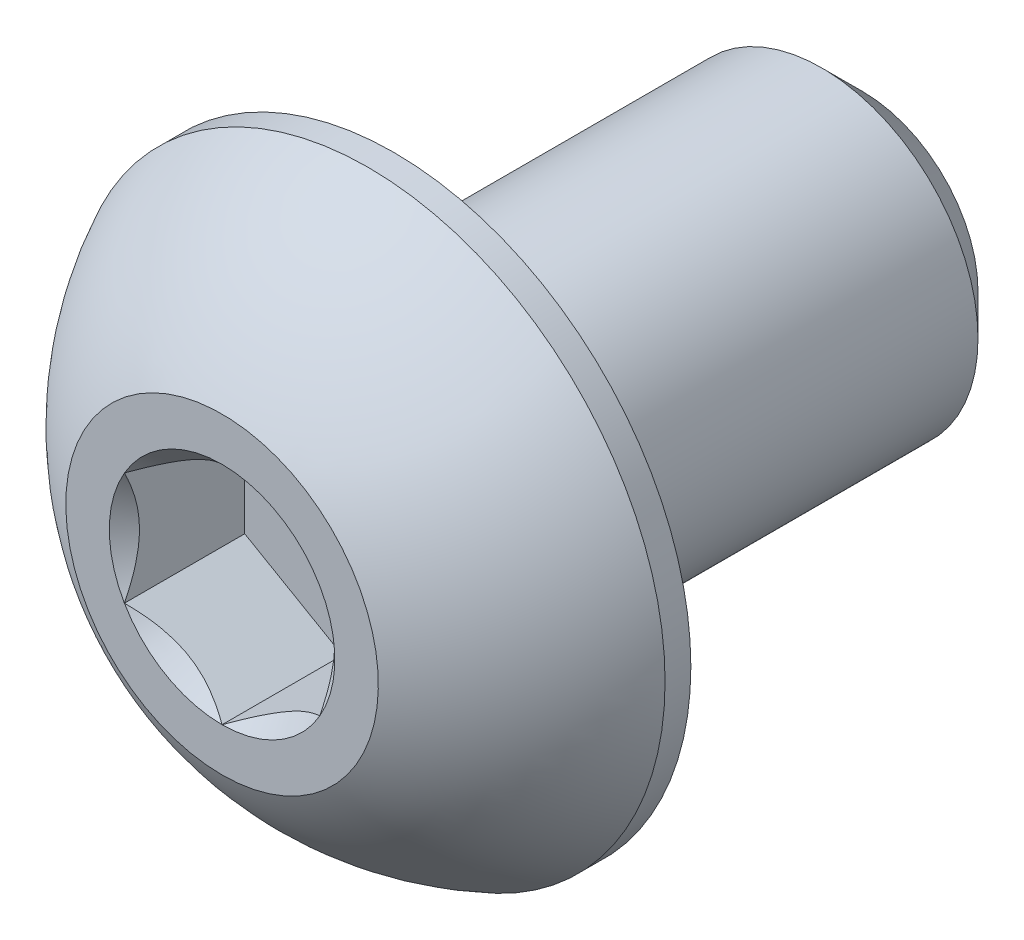
SolidWorks part; units mm, degrees
ref_plane "Front" through (0, 0, 0) normal (0, 0, 1) x (1, 0, 0)
ref_plane "Top" through (0, 0, 0) normal (0, 1, 0) x (1, 0, 0)
ref_plane "Right" through (0, 0, 0) normal (1, 0, 0) x (0, 0, -1)
sketch "Sketch1" plane through (0, 0, 0) normal (1, 0, 0) x (0, 0, -1)
  line L2 (2.2, 2) -> (8.2, 2)
  line L3 (8.2, 2) -> (8.2, 0)
  line L4 (8.2, 0) -> (2.2, 0)
  line L6 (1.87, 3.8) -> (2.2, 3.8) construction
  line L7 (8.2, 2) -> (8.2, -2) construction
  line L8 (0, 0) -> (2.2, 0) construction
  line L9 (2.2, 3.8) -> (2.2, -3.8) construction
  line L11 (2.2, 2) -> (2.2, 0)
  line L13 (0, 1.25) -> (0, -1.25) construction
  line L14 (0, 1.25) -> (0, 2) construction
  line L15 (8.1562, 2.0758) -> (8.5062, 1.4696) construction
  line L16 (8.5062, 1.4696) -> (8.8562, 2.0758) construction
  line L17 (8.8562, 2.0758) -> (8.1562, 2.0758) construction
  line L18 (8.2, 2) -> (8.8125, 2) construction
  line L19 (8.5062, 2.0758) -> (8.5062, 2) construction
  line L20 (8.5062, 2) -> (8.5062, 1.5453) construction
  line L21 (8.5062, 1.5453) -> (8.5062, 1.4696) construction
  line L22 (8.4625, 1.5453) -> (8.55, 1.5453)
  line L23 (8.1781, 2.0379) -> (8.8344, 2.0379)
  line L24 (8.55, 1.5453) -> (8.8344, 2.0379)
  line L25 (8.4625, 1.5453) -> (8.1781, 2.0379)
  line L26 (7.675, 2) -> (8.2, 1.475)
  arc A3 (0, 2) -> (1.87, 3.8) centre (3.7264, 0) cw construction
  point P29 (8.5062, 2.0379)
  point P30 (6.45, -2)
  dimension "D1" = 0.33
  dimension "Pitch" = 0.7
  dimension "D3" = 0.0875
  dimension "D2" = 0.525
  dimension "D4" = 45
  dimension "D5" = 1.75
sketch "Sketch10" plane through (0, 0, 0) normal (1, 0, 0) x (0, 0, -1)
  line L0 (7.675, 2) -> (8.2, 1.475) construction
  line L1 (7.675, 2) -> (8.2, 1.475)
  line L4 (8.2, 2) -> (2.2, 2)
  line L5 (8.2, 0) -> (8.2, 2)
  line L6 (2.2, 0) -> (8.2, 0)
  line L7 (2.2, 2) -> (2.2, 0)
  line L8 (7.675, 2) -> (2.2, 2)
  line L9 (8.2, 0) -> (8.2, 1.475)
  line L10 (2.2, 0) -> (8.2, 0)
  line L11 (2.2, 2) -> (2.2, 0)
  dimension "D1" = 0
revolve "Revolve3" add sketch "Sketch10" angle 360 about L8
sketch "Sketch7" plane through (0, 0, 0) normal (1, 0, 0) x (0, 0, -1)
  line L6 (1.87, 3.8) -> (2.2, 3.8) construction
  line L8 (0, 0) -> (2.2, 0) construction
  line L11 (2.2, 3.8) -> (2.2, -3.8) construction
  line L12 (1.87, 3.8) -> (2.2, 3.8)
  line L13 (0, 0) -> (2.2, 0)
  line L14 (0, 1.25) -> (0, -1.25) construction
  line L15 (2.2, 3.8) -> (2.2, 0)
  line L16 (0, 2) -> (0, 0)
  arc A2 (1.87, 3.8) -> (0, 2) centre (3.7264, 0) ccw construction
  arc A3 (1.87, 3.8) -> (0, 2) centre (3.7264, 0) ccw
revolve "Revolve2" add sketch "Sketch7" angle 360 mid plane about L13
sketch "Sketch5" plane through (0, 0, 0) normal (0, 0, 1) x (1, 0, 0)
  line L1 (1.25, -0.7217) -> (1.25, 0.7217)
  line L2 (1.25, 0.7217) -> (0, 1.4434)
  line L3 (0, 1.4434) -> (-1.25, 0.7217)
  line L4 (-1.25, 0.7217) -> (-1.25, -0.7217)
  line L5 (-1.25, -0.7217) -> (0, -1.4434)
  line L6 (0, -1.4434) -> (1.25, -0.7217)
  circle A0 centre (0, 0) radius 1.25 construction
extrude "Cut-Extrude2" cut sketch "Sketch5" against normal blind 1.54
sketch "Sketch6" plane through (0, 0, 0) normal (0, 0, 1) x (1, 0, 0)
  circle A0 centre (0, 0) radius 1.4434
extrude "Cut-Extrude3" cut sketch "Sketch6" against normal blind 1.54 draft 45
sketch "Sketch9" [suppressed] plane through (0, 0, -2.2) normal (0, 0, -1) x (-1, 0, 0)
  circle A0 centre (0, 0) radius 2 construction
  circle A4 centre (0, 0) radius 2
split "Split1" [suppressed] bodies to split 113
sketch "Sketch11" [suppressed] plane through (0, 0, -8.2) normal (0, 0, -1) x (-1, 0, 0)
  circle A0 centre (0, 0) radius 2 construction
  circle A1 centre (0, 0) radius 2
curve "Helix/Spiral1" [suppressed] pitch 0.7 height 8.2 turns 11.7143
sketch "Sketch12" [suppressed] plane through (0, 0, 0) normal (1, 0, 0) x (0, 0, -1)
  line L0 (8.4625, 1.5453) -> (8.55, 1.5453) construction
  line L1 (8.55, 1.5453) -> (8.8344, 2.0379) construction
  line L2 (8.1781, 2.0379) -> (8.8344, 2.0379) construction
  line L3 (8.4625, 1.5453) -> (8.1781, 2.0379) construction
  line L4 (8.4625, 1.5453) -> (8.55, 1.5453)
  line L5 (8.55, 1.5453) -> (8.8344, 2.0379)
  line L6 (8.1781, 2.0379) -> (8.8344, 2.0379)
  line L7 (8.4625, 1.5453) -> (8.1781, 2.0379)
sweep "Cut-Sweep2" [suppressed] cut profiles "Sketch12" path "Helix/Spiral1"
extrude "Boss-Extrude1" [suppressed] add sketch "Sketch9" along normal blind 10 draft 45
equation "\"D1@Cut-Extrude2\" = \"Head Ht@Sketch1\" * .7"
equation "\"D1@Sketch1\" = \"Head Ht@Sketch1\" * .15"
equation "\"D1@Cut-Extrude3\" = \"D1@Cut-Extrude2\""
equation "\"D3@Sketch1\" = \"Pitch@Sketch1\" / 8"
equation "\"D2@Sketch1\"=\"Pitch@Sketch1\"*0.75"
equation "\"D3@Helix/Spiral1\" = \"Lg@Sketch1\" + \"Head Ht@Sketch1\""
equation "\"D4@Helix/Spiral1\"=\"pitch@sketch1\""
equation "\"D5@Sketch1\"=\"Pitch@Sketch1\"*2.5"
